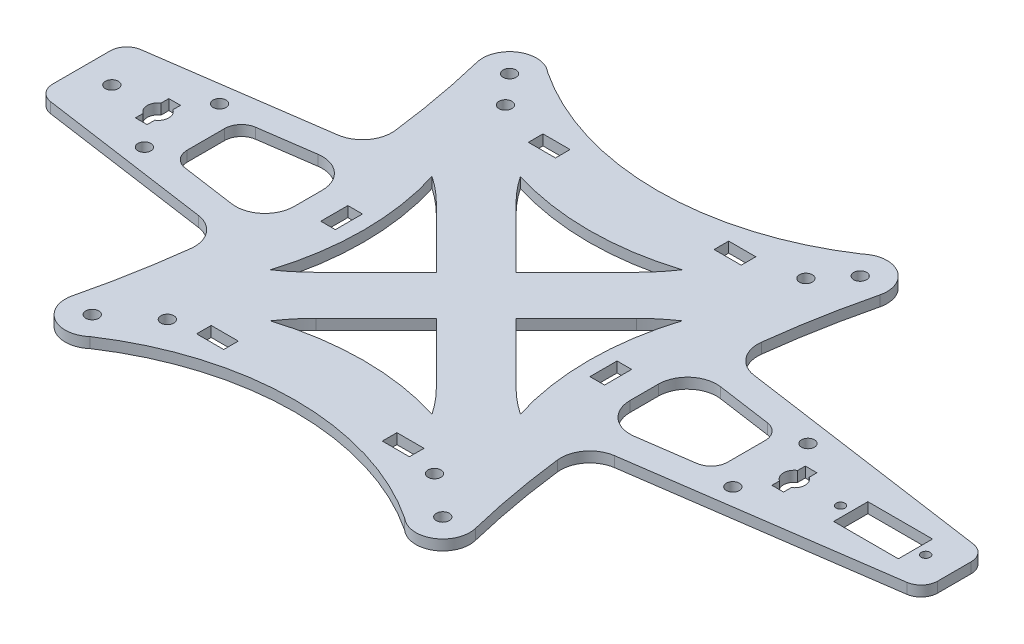
SolidWorks part; units mm, degrees
material "PPS"
ref_plane "前视基准面" through (0, 0, 0) normal (0, 0, 1) x (1, 0, 0)
ref_plane "上视基准面" through (0, 0, 0) normal (0, 1, 0) x (1, 0, 0)
ref_plane "右视基准面" through (0, 0, 0) normal (1, 0, 0) x (0, 0, -1)
sketch "草图1" plane through (0, 0, 0) normal (0, 1, 0) x (1, 0, 0)
  line L3 (-133.7177, 0) -> (146.3754, 0) construction
  line L56 (0, 96.0639) -> (0, -115.1457) construction
  line L65 (-25.5, 41.5) -> (-19, 41.5)
  line L66 (-34, 3.25) -> (-30.5, 3.25)
  line L70 (-34, 3.25) -> (-34, -3.25)
  line L76 (-34, -3.25) -> (-30.5, -3.25)
  line L80 (-30.5, 3.25) -> (-30.5, -3.25)
  line L81 (-25.5, -38) -> (-19, -38)
  line L82 (-25.5, -38) -> (-25.5, -41.5)
  line L83 (-25.5, -41.5) -> (-19, -41.5)
  line L84 (-19, -38) -> (-19, -41.5)
  line L85 (-19, 38) -> (-19, 41.5)
  line L86 (-25.5, 38) -> (-19, 38)
  line L142 (-25.5, 38) -> (-25.5, 41.5)
  line L143 (25.5, 38) -> (25.5, 41.5)
  line L144 (25.5, 38) -> (19, 38)
  line L145 (19, 38) -> (19, 41.5)
  line L146 (19, -38) -> (19, -41.5)
  line L147 (25.5, -41.5) -> (19, -41.5)
  line L148 (25.5, -38) -> (25.5, -41.5)
  line L149 (25.5, -38) -> (19, -38)
  line L150 (30.5, 3.25) -> (30.5, -3.25)
  line L151 (34, -3.25) -> (30.5, -3.25)
  line L152 (34, 3.25) -> (34, -3.25)
  line L153 (34, 3.25) -> (30.5, 3.25)
  line L154 (25.5, 41.5) -> (19, 41.5)
  line L155 (77.65, -2.1518) -> (77.65, -4)
  line L156 (74.85, 4) -> (77.65, 4)
  line L157 (74.85, 4) -> (74.85, 2.1768)
  line L158 (74.85, -4) -> (77.65, -4)
  line L159 (77.65, 4) -> (77.65, 2.1518)
  line L160 (74.85, -2.1768) -> (74.85, -4)
  line L161 (97.5, 7.6653) -> (97.5, -9.1503) construction
  line L162 (89.75, 4.1) -> (105.25, 4.1)
  line L163 (89.75, 4.1) -> (89.75, -4.1)
  line L164 (89.75, -4.1) -> (105.25, -4.1)
  line L165 (105.25, 4.1) -> (105.25, -4.1)
  line L166 (-97.5, 7.6653) -> (-97.5, -9.1503) construction
  line L171 (-74.85, -2.1768) -> (-74.85, -4)
  line L172 (-77.65, 4) -> (-77.65, 2.1518)
  line L173 (-74.85, -4) -> (-77.65, -4)
  line L174 (-74.85, 4) -> (-74.85, 2.1768)
  line L175 (-74.85, 4) -> (-77.65, 4)
  line L176 (-77.65, -2.1518) -> (-77.65, -4)
  line L177 (114.5911, 7.4683) -> (114.5911, -7.4683)
  line L178 (114.5911, 7.4683) -> (43.1936, 17.6463)
  line L179 (114.5911, -7.4683) -> (43.1936, -17.6463)
  line L183 (-23.978, 14.4296) -> (-9.5485, 0)
  line L184 (14.4296, 23.978) -> (0, 9.5485)
  line L185 (-23.978, -14.4296) -> (-9.5485, 0)
  line L186 (-14.4296, 23.978) -> (0, 9.5485)
  line L187 (23.978, -14.4296) -> (9.5485, 0)
  line L188 (23.978, 14.4296) -> (9.5485, 0)
  line L189 (-14.4296, -23.978) -> (0, -9.5485)
  line L190 (14.4296, -23.978) -> (0, -9.5485)
  line L191 (-94.5795, 10.321) -> (-94.5795, -10.321)
  line L192 (-43.1936, 17.6463) -> (-94.5795, 10.321)
  line L193 (-94.5795, -10.321) -> (-43.1936, -17.6463)
  line L195 (-64.75, -7.9571) -> (-64.75, 7.9571)
  line L196 (-64.75, 7.9571) -> (-40.25, 11.4497)
  line L197 (-40.25, 11.4497) -> (-40.25, -11.4497)
  line L198 (-64.75, -7.9571) -> (-40.25, -11.4497)
  line L199 (64.75, 7.9571) -> (40.25, 11.4497)
  line L200 (40.25, 11.4497) -> (40.25, -11.4497)
  line L201 (64.75, -7.9571) -> (40.25, -11.4497)
  line L202 (64.75, 7.9571) -> (64.75, -7.9571)
  circle A0 centre (-36, 43) radius 1.55
  circle A1 centre (-32, -42) radius 1.55
  circle A2 centre (32, -42) radius 1.55
  circle A3 centre (36, 43) radius 1.55
  circle A4 centre (42, 50) radius 1.55
  circle A5 centre (42, -50) radius 1.55
  circle A6 centre (-42, -50) radius 1.55
  circle A7 centre (-42, 50) radius 1.55
  arc A8 (74.85, 2.1768) -> (74.85, -2.1768) centre (76.2307, 0) ccw
  arc A9 (77.65, -2.1518) -> (77.65, 2.1518) centre (76.2307, 0) ccw
  circle A10 centre (107.7, 0) radius 1.05
  circle A11 centre (87.3, 0) radius 1.05
  circle A12 centre (-87.3, 0) radius 1.05 construction
  arc A14 (-77.65, -2.1518) -> (-77.65, 2.1518) centre (-76.2307, 0) cw
  arc A15 (-74.85, 2.1768) -> (-74.85, -2.1768) centre (-76.2307, 0) cw
  arc A18 (-37.7098, 54.831) -> (37.7098, 54.831) centre (0, 111.5317) ccw
  arc A20 (48.2756, 48.4632) -> (43.1936, 17.6463) centre (246.1791, 0) ccw
  arc A21 (48.2756, 48.4632) -> (37.7098, 54.831) centre (42, 50) ccw
  arc A22 (-37.7098, -54.831) -> (37.7098, -54.831) centre (0, -111.5317) cw
  arc A23 (48.2756, -48.4632) -> (43.1936, -17.6463) centre (246.1791, 0) cw
  arc A24 (48.2756, -48.4632) -> (37.7098, -54.831) centre (42, -50) cw
  arc A26 (-48.2756, -48.4632) -> (-37.7098, -54.831) centre (-42, -50) ccw
  arc A27 (-48.2756, -48.4632) -> (-43.1936, -17.6463) centre (-246.1791, 0) ccw
  arc A28 (-48.2756, 48.4632) -> (-37.7098, 54.831) centre (-42, 50) cw
  arc A30 (-48.2756, 48.4632) -> (-43.1936, 17.6463) centre (-246.1791, 0) cw
  arc A31 (-23.978, 14.4296) -> (-29.9602, 19.3706) centre (-52.8883, -14.4807) ccw
  arc A32 (-23.978, -14.4296) -> (-29.9602, -19.3706) centre (-52.8883, 14.4807) cw
  arc A33 (-29.9602, -19.3706) -> (-29.9602, 19.3706) centre (-91.9966, 0) ccw
  arc A34 (-14.4296, 23.978) -> (-19.3706, 29.9602) centre (14.4807, 52.8883) cw
  arc A35 (-19.3706, 29.9602) -> (19.3706, 29.9602) centre (0, 91.9966) ccw
  arc A36 (14.4296, 23.978) -> (19.3706, 29.9602) centre (-14.4807, 52.8883) ccw
  arc A37 (23.978, 14.4296) -> (29.9602, 19.3706) centre (52.8883, -14.4807) cw
  arc A38 (29.9602, 19.3706) -> (29.9602, -19.3706) centre (91.9966, 0) ccw
  arc A39 (23.978, -14.4296) -> (29.9602, -19.3706) centre (52.8883, 14.4807) ccw
  arc A40 (14.4296, -23.978) -> (19.3706, -29.9602) centre (-14.4807, -52.8883) cw
  arc A41 (19.3706, -29.9602) -> (-19.3706, -29.9602) centre (0, -91.9966) ccw
  arc A42 (-14.4296, -23.978) -> (-19.3706, -29.9602) centre (14.4807, -52.8883) ccw
  circle A43 centre (70.5, 9) radius 1.55
  circle A44 centre (70.5, -9) radius 1.55
  circle A45 centre (-70.5, -9) radius 1.55
  circle A46 centre (-70.5, 9) radius 1.55
  circle A47 centre (-87.3, 0) radius 1.55
  point P81 (-34, 0)
  point P118 (0, 0)
  point P140 (-40.25, 0)
  point P149 (-64.75, 0)
  dimension "D5" = 38
  dimension "D18" = 8.2
  dimension "D24" = 3.1
  dimension "D6" = 3.1
  dimension "D11" = 50
  dimension "D15" = 74.85
  dimension "D16" = 2.1
  dimension "D17" = 15.5
  dimension "D21" = 3.1
  dimension "D1" = 6.5
  dimension "D2" = 3.5
  dimension "D3" = 30.5
  dimension "D4" = 19
  dimension "D7" = 32
  dimension "D8" = 42
  dimension "D9" = 43
  dimension "D10" = 36
  dimension "D12" = 42
  dimension "D13" = 2.8
  dimension "D14" = 4
  dimension "D19" = 2.45
  dimension "D20" = 97.5
  dimension "D22" = 9
  dimension "D23" = 70.5
  dimension "D25" = 6.55
  dimension "D26" = 5.75
  dimension "D27" = 6.25
  dimension "D28" = 4
extrude "凸台-拉伸1" add sketch "草图1" along normal blind 2.5
fillet "圆角1" radius 4 8 edges at (114.5911, 1.25, -7.4683) (114.5911, 1.25, 7.4683) (-94.5795, 1.25, 10.321) (-94.5795, 1.25, -10.321) (-64.75, 1.25, 7.9571) (-64.75, 1.25, -7.9571) (64.75, 1.25, 7.9571) (64.75, 1.25, -7.9571)
fillet "圆角2" radius 7 8 edges at (43.1936, 1.25, -17.6463) (43.1936, 1.25, 17.6463) (-43.1936, 1.25, 17.6463) (-43.1936, 1.25, -17.6463) (40.25, 1.25, 11.4497) (40.25, 1.25, -11.4497) (-40.25, 1.25, 11.4497) (-40.25, 1.25, -11.4497)
